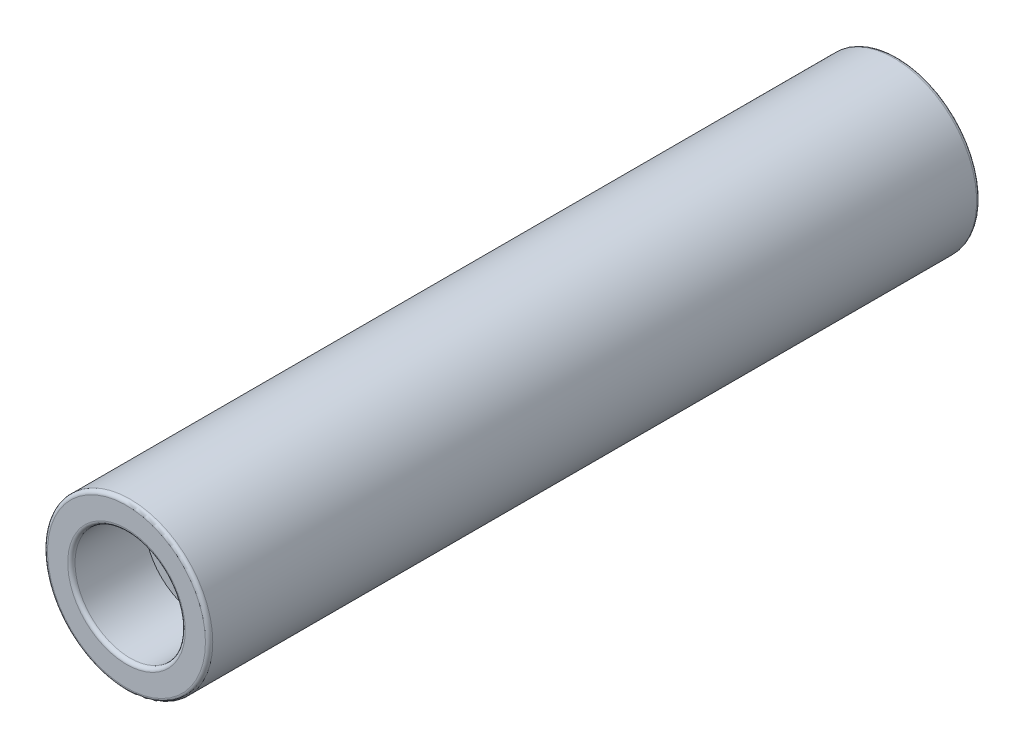
SolidWorks part; units mm, degrees
ref_plane "Front Plane" through (0, 0, 0) normal (0, 0, 1) x (1, 0, 0)
ref_plane "Top Plane" through (0, 0, 0) normal (0, 1, 0) x (1, 0, 0)
ref_plane "Right Plane" through (0, 0, 0) normal (1, 0, 0) x (0, 0, -1)
sketch "Sketch1" plane through (0, 0, 0) normal (0, 0, 1) x (1, 0, 0)
  circle A0 centre (0, 0) radius 4.5
  dimension "D1" = 9
extrude "Extrude-Thin1" add sketch "Sketch1" along normal blind 12 thin contours A0 thin type one direction reverse wall 3.75
sketch "Sketch11" plane through (0, 0, 12) normal (0, 0, 1) x (1, 0, 0)
  circle A0 centre (0, 0) radius 1.5
  dimension "D1" = 3
extrude "Extrude-Thin3" add sketch "Sketch11" along normal blind 5 thin thin type one direction wall 3
sketch "Sketch12" plane through (0, 0, 17) normal (0, 0, 1) x (1, 0, 0)
  circle A0 centre (0, 0) radius 3
  dimension "D1" = 6
extrude "Extrude-Thin4" add sketch "Sketch12" along normal blind 4 thin thin type one direction wall 1.5
thread "Thread1" pitch 0.5 method extrude profile "Thread Profile1" start angle 0, offset 0, length 5, pitch 0.5, diameter 3
ref_plane "Plane6" through (1.5, 0, 12) normal (0, -1, 0) x (1, 0, 0)
sketch "Thread Profile1" plane through (1.5, 0, 12) normal (0, -1, 0) x (1, 0, 0)
  line L0 (0, 0) -> (0, 0.5) construction
  line L11 (0, 0) -> (0, 0.4375)
  line L12 (0, 0.4375) -> (-0.2706, 0.2812)
  line L13 (-0.2706, 0.2812) -> (-0.2706, 0.1562)
  line L15 (-0.2706, 0.1562) -> (0, 0)
  line L17 (-0.2706, 0.2187) -> (0, 0.2187) construction
  point P2 (0, 0)
  dimension "Pitch" = 0.5
  dimension "Profile_Angle" = 60
  dimension "Profile_Land" = 0.125
  dimension "Profile_Height" = 0.2706
mirror "Mirror2" about plane through (0, 0, 0) normal (0, 0, 1) of "Extrude-Thin4", "Extrude-Thin3", "Thread1", "Extrude-Thin1"
fillet "Fillet1" radius 0.2 4 edges at (4.5, 0, -21) (3, 0, -21) (4.5, 0, 21) (3, 0, 21)
